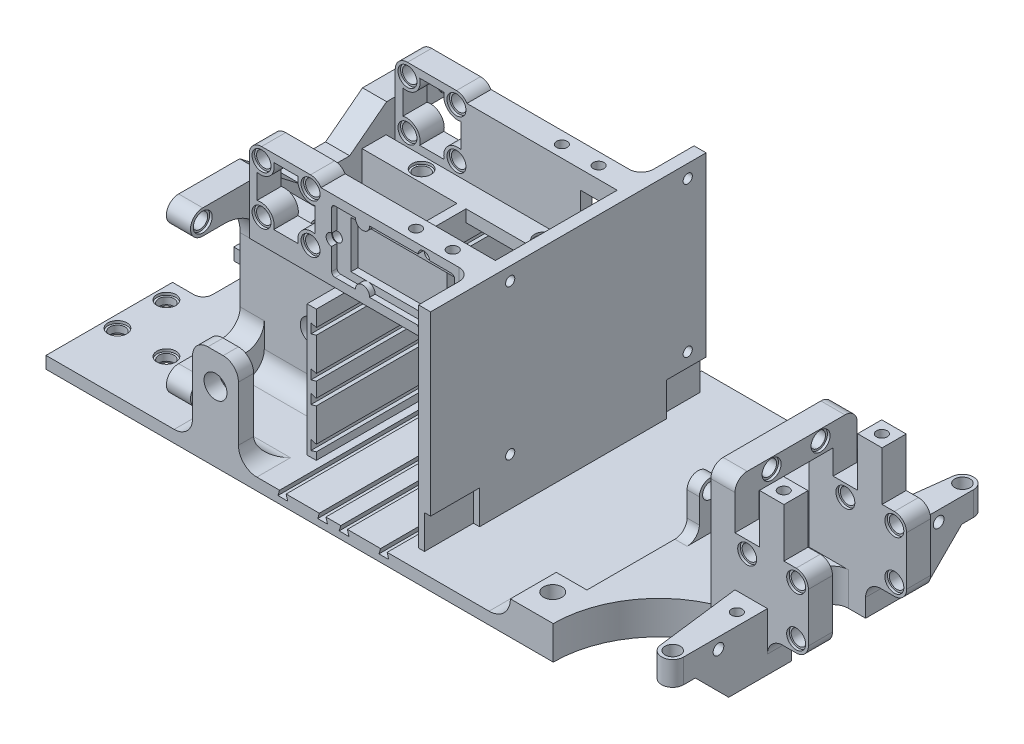
SolidWorks part; units mm, degrees
note: The reader was unsure of these and kept them because the rebuilt part matched: shared geometry of "Croquis3<3>", "Croquis3<4>", "Croquis4<3>", "Croquis6<5>", "Croquis10<3>", "Croquis12<5>", "Croquis12<4>", "Croquis13<5>", "Croquis14<3>", "Croquis25<3>", "Croquis30<3>", "Croquis24<4>", "Croquis30<5>".
material "PET"
ref_plane "Alzado" through (0, 0, 0) normal (0, 0, 1) x (1, 0, 0)
ref_plane "Planta" through (0, 0, 0) normal (0, 1, 0) x (1, 0, 0)
ref_plane "Vista lateral" through (0, 0, 0) normal (1, 0, 0) x (0, 0, -1)
sketch "Croquis1" plane through (0, 0, 0) normal (0, 0, 1) x (1, 0, 0)
  circle A0 centre (0, 15) radius 14.5 construction
  circle A1 centre (0, 15) radius 15 construction
  dimension "D2" = 30
  dimension "D3" = 29
  dimension "D1" = 15
sketch "Croquis2" plane through (0, 0, 0) normal (0, 1, 0) x (1, 0, 0)
  line L0 (-14.5, 0) -> (14.5, 0) construction
  line L1 (-15.5, 12.05) -> (15.5, 12.05)
  line L2 (-15.5, 12.05) -> (-15.5, -12.05)
  line L3 (-15.5, -12.05) -> (15.5, -12.05)
  line L4 (15.5, 12.05) -> (15.5, -12.05)
  line L5 (-15.5, 12.05) -> (15.5, -12.05) construction
  line L6 (-15.5, -12.05) -> (15.5, 12.05) construction
  line L7 (-23.37, 19.9) -> (18.5, 19.9)
  line L9 (-23.37, -19.9) -> (18.5, -19.9)
  line L11 (23.35, 19.9) -> (23.35, -19.9) construction
  line L12 (-23.35, 19.9) -> (-23.35, -19.9) construction
  line L13 (-23.37, 19.9) -> (-23.37, -19.9)
  line L14 (18.5, -19.9) -> (18.5, 19.9)
  line L16 (-23.35, 19.9) -> (23.35, 19.9) construction
  line L17 (-23.35, -19.9) -> (23.35, -19.9) construction
  point P0 (0, 0)
  dimension "D1" = 31
  dimension "D2" = 24.1
  dimension "D4" = 39.8
  dimension "D5" = 3
  dimension "D6" = 7.87
  dimension "D3" = 7.85
extrude "Saliente-Extruir1" add sketch "Croquis2" along normal blind 42.87 and the other way blind 3.9
sketch "Croquis5" plane through (0, 0, 19.9) normal (0, 0, 1) x (1, 0, 0)
  circle A0 centre (0, 15) radius 3.75
  dimension "D1" = 7.5
extrude "Cortar-Extruir4" cut sketch "Croquis5" against normal through all
sketch "Croquis3" plane through (0, 42.87, 0) normal (0, 1, 0) x (1, 0, 0)
  line L1 (-15.5, 0) -> (15.5, 0) construction
  line L2 (-15.5, 12.05) -> (-15.5, -12.05) construction
  line L3 (15.5, -12.05) -> (15.5, 12.05) construction
  circle A0 centre (0, -16) radius 2.485
  circle A1 centre (0, -16) radius 3.1
  dimension "D2" = 6.2
  dimension "D1" = 16
  dimension "D3" = 4.97
extrude "Cortar-Extruir1" cut sketch "Croquis3" against normal blind 7.87 contours A0
extrude "Cortar-Extruir2" cut sketch "Croquis3<3>" against normal blind 0.85 contours A0 | A1
sketch "Croquis3<3>" plane through (0, 42.87, 0) normal (0, 1, 0) x (1, 0, 0) same geometry as "Croquis3"
extrude "Cortar-Extruir3" cut sketch "Croquis3<4>" along normal blind 0.85 from offset 7.87 offset against normal yes
sketch "Croquis3<4>" plane through (0, 42.87, 0) normal (0, 1, 0) x (1, 0, 0) same geometry as "Croquis3"
mirror "Simetría1" about plane through (0, 0, 0) normal (0, 0, 1) of "Cortar-Extruir3", "Cortar-Extruir2", "Cortar-Extruir1"
sketch "Croquis4" plane through (0, 42.87, 0) normal (0, 1, 0) x (1, 0, 0)
  line L0 (-23.37, -19.9) -> (18.5, -19.9) construction
  line L6 (18.4996, -19.9) -> (60, -19.9)
  line L7 (18.4996, -19.9) -> (18.4996, -12)
  line L8 (18.4996, -12) -> (60, -12)
  line L9 (60, -19.9) -> (60, -12)
  circle A0 centre (40, -16) radius 2.485
  circle A1 centre (0, -16) radius 3.1 construction
  circle A2 centre (40, -16) radius 3.1
  circle A3 centre (56, -16) radius 2.485
  circle A4 centre (56, -16) radius 3.1
  point P14 (0, 0)
  dimension "D4" = 4.97
  dimension "D7" = 4
  dimension "D5" = 6.2
  dimension "D1" = 7.9
  dimension "D2" = 40
  dimension "D3" = 16
  dimension "D6" = 16
extrude "Saliente-Extruir2" add sketch "Croquis4" against normal blind 3.935
extrude "Saliente-Extruir3" add sketch "Croquis4<3>" against normal offset from surface (2.235 mm away) 0.85 from offset 0.85 contours A2 | A0 | A4 | A3 up to face at (56, 38.935, 19.1) offset against normal yes
sketch "Croquis4<3>" plane through (0, 42.87, 0) normal (0, 1, 0) x (1, 0, 0) same geometry as "Croquis4"
mirror "Simetría11" about plane through (0, 0, 0) normal (0, 0, 1) of "Saliente-Extruir2"
mirror "Simetría13" about plane through (0, 0, 0) normal (0, 0, 1) of "Saliente-Extruir3"
ref_plane "Plano2" through (0, -7.8, 0) normal (0, 1, 0) x (1, 0, 0)
sketch "Croquis6" plane through (0, -7.8, 0) normal (0, 1, 0) x (1, 0, 0)
  line L1 (-55.37, -51.335) -> (138.33, -51.335)
  line L2 (-55.37, -51.335) -> (-55.37, 51.335)
  line L5 (-23.37, 19.9) -> (-23.37, -19.9) construction
  line L6 (0, 0) -> (-55.37, 0) construction
  line L7 (-55.37, 51.335) -> (138.33, 51.335)
  line L8 (-15.5, 12.05) -> (15.5, 12.05)
  line L9 (-15.5, 12.05) -> (-15.5, -12.05)
  line L10 (-15.5, -12.05) -> (15.5, -12.05)
  line L11 (15.5, 12.05) -> (15.5, -12.05)
  line L12 (138.33, 51.335) -> (138.33, -51.335)
  circle A0 centre (-51.37, -16) radius 3.1
  circle A2 centre (-51.37, -32) radius 3.1
  circle A3 centre (-35.37, -32) radius 3.1
  circle A4 centre (-35.37, -32) radius 2.485
  circle A5 centre (-51.37, -32) radius 2.485
  circle A7 centre (-51.37, -16) radius 2.485
  circle A8 centre (-51.37, 16) radius 2.485
  circle A10 centre (-51.37, 32) radius 2.485
  circle A11 centre (-35.37, 32) radius 2.485
  circle A12 centre (-35.37, 32) radius 3.1
  circle A13 centre (-51.37, 32) radius 3.1
  circle A15 centre (-51.37, 16) radius 3.1
  dimension "D5" = 4.97
  dimension "D6" = 6.2
  dimension "D1" = 102.67
  dimension "D2" = 51.335
  dimension "D4" = 193.7
  dimension "D10" = 16
  dimension "D8" = 16
  dimension "D7" = 16
  dimension "D9" = 4
  dimension "D3" = 32
extrude "Saliente-Extruir4" add sketch "Croquis6" along normal blind 3.935
extrude "Saliente-Extruir6" add sketch "Croquis6<5>" along normal offset from surface (2.235 mm away) 0.85 from offset 0.85 contours A2 A5 | A0 A7 | A3 A4 | A12 A11 | A13 A10 | A15 A8
sketch "Croquis6<5>" plane through (0, -7.8, 0) normal (0, 1, 0) x (1, 0, 0) same geometry as "Croquis6"
sketch "Croquis9" plane through (0, -7.8, 0) normal (0, -1, 0) x (1, 0, 0)
  line L0 (-55.37, 51.335) -> (-55.37, -51.335) construction
  line L1 (-55.37, 10) -> (-48.37, 10)
  line L2 (-55.37, 10) -> (-55.37, -10)
  line L3 (-55.37, -10) -> (-48.37, -10)
  line L4 (-45.37, 7) -> (-45.37, -7)
  arc A0 (-48.37, -10) -> (-45.37, -7) centre (-48.37, -7) ccw
  arc A1 (-48.37, 10) -> (-45.37, 7) centre (-48.37, 7) cw
  point P6 (-55.37, 0)
  point P12 (-45.37, 10)
  dimension "D3" = 3
  dimension "D1" = 20
  dimension "D2" = 10
extrude "Cortar-Extruir7" cut sketch "Croquis9" against normal up to next
sketch "Croquis10" plane through (-23.37, 0, 0) normal (-1, 0, 0) x (0, 0, 1)
  line L0 (-19.9, -3.865) -> (-19.9, 42.87) construction
  line L1 (-19.9, 4.135) -> (-40, 4.135)
  line L3 (-10, -3.865) -> (-51.335, -3.865) construction
  line L4 (-40, -3.865) -> (-19.9, -3.865)
  line L5 (-19.9, -3.865) -> (-19.9, 4.135)
  line L6 (-8, 42.87) -> (-20.0744, 52.135)
  line L8 (-20.0744, 52.135) -> (-40, 52.135)
  line L9 (-40, 44.135) -> (-32.9, 44.135)
  line L10 (-19.9, 31.135) -> (-19.9, 42.87)
  line L11 (-19.9, 42.87) -> (-8, 42.87)
  line L12 (0, 0) -> (0, 42.87) construction
  line L13 (-19.9, 42.87) -> (19.9, 42.87) construction
  circle A0 centre (-40, 48.135) radius 2.485
  circle A1 centre (-40, 0.135) radius 2.485
  circle A4 centre (-40, 48.135) radius 3.1
  circle A5 centre (-40, 0.135) radius 3.1
  arc A9 (-40, 52.135) -> (-40, 44.135) centre (-40, 48.135) ccw
  arc A10 (-32.9, 44.135) -> (-19.9, 31.135) centre (-32.9, 31.135) cw
  arc A11 (-40, 4.135) -> (-40, -3.865) centre (-40, 0.135) ccw
  point P10 (0, 0)
  point P11 (0, 42.87)
  point P18 (0, 42.87)
  dimension "D1" = 4.97
  dimension "D2" = 6.2
  dimension "D8" = 4
  dimension "D10" = 13
  dimension "D7" = 8
  dimension "D9" = 35
  dimension "D11" = 8
  dimension "D3" = 40
  dimension "D4" = 48
  dimension "D5" = 4
  dimension "D6" = 37.5
  dimension "D12" = 40
extrude "Saliente-Extruir7" add sketch "Croquis10" against normal blind 7.87
extrude "Saliente-Extruir8" add sketch "Croquis10<3>" against normal offset from surface (6.17 mm away) 0.85 from offset 0.85 contours A5 A1 | A4 A0 up to face at (-15.5, 0.135, -36.9) offset against normal yes
sketch "Croquis10<3>" plane through (-23.37, 0, 0) normal (-1, 0, 0) x (0, 0, 1) same geometry as "Croquis10"
mirror "Simetría14" about plane through (0, 0, 0) normal (0, 0, 1) of "Saliente-Extruir8", "Saliente-Extruir7"
sketch "Croquis12" plane through (0, 0, 19.9) normal (0, 0, 1) x (1, 0, 0)
  line L0 (-23.37, 44.135) -> (-23.37, 31.135) construction
  line L1 (-15.5, 42.87) -> (60, 42.87) construction
  line L2 (-0.52, 38.935) -> (-0.52, 66.87) construction
  line L3 (-8.52, 66.87) -> (7.48, 66.87)
  line L4 (-12.52, 62.87) -> (-12.52, 38.935)
  line L5 (-12.52, 38.935) -> (11.48, 38.935)
  line L6 (11.48, 62.87) -> (11.48, 38.935)
  line L7 (11.48, 54.87) -> (-12.52, 54.87) construction
  line L8 (3.48, 45.37) -> (-4.52, 45.37)
  line L9 (-10.02, 50.87) -> (-10.02, 58.87)
  line L10 (8.98, 50.87) -> (8.98, 58.87)
  line L11 (3.48, 64.37) -> (-4.52, 64.37)
  line L12 (18.5, 38.935) -> (60, 38.935) construction
  circle A0 centre (-8.52, 62.87) radius 2.485
  circle A1 centre (-8.52, 62.87) radius 3.1
  circle A2 centre (7.48, 62.87) radius 2.485
  circle A3 centre (7.48, 62.87) radius 3.1
  circle A4 centre (7.48, 46.87) radius 2.485
  circle A5 centre (7.48, 46.87) radius 3.1
  circle A6 centre (-8.52, 46.87) radius 2.485
  circle A7 centre (-8.52, 46.87) radius 3.1
  arc A8 (7.48, 66.87) -> (11.48, 62.87) centre (7.48, 62.87) cw
  arc A9 (-8.52, 66.87) -> (-12.52, 62.87) centre (-8.52, 62.87) ccw
  arc A10 (-4.52, 45.37) -> (-10.02, 50.87) centre (-8.8708, 46.5192) ccw
  arc A11 (3.48, 45.37) -> (8.98, 50.87) centre (7.8308, 46.5192) cw
  arc A12 (3.48, 64.37) -> (8.98, 58.87) centre (7.8308, 63.2208) ccw
  arc A13 (-4.52, 64.37) -> (-10.02, 58.87) centre (-8.8708, 63.2208) cw
  point P34 (-0.52, 45.37)
  point P38 (8.98, 54.87)
  point P43 (-10.02, 54.87)
  line M31 (60, 42.87) -> (-15.5, 42.87)
  dimension "D8" = 4
  dimension "D3" = 6.2
  dimension "D4" = 4.97
  dimension "D10" = 4
  dimension "D17" = 4.5
  dimension "D1" = 16
  dimension "D2" = 16
  dimension "D5" = 14.85
  dimension "D6" = 4
  dimension "D7" = 4
  dimension "D9" = 4
  dimension "D12" = 12
  dimension "D13" = 2.5
  dimension "D14" = 4
  dimension "D15" = 4
  dimension "D16" = 2.5
extrude "Saliente-Extruir11" add sketch "Croquis12" along normal blind 7.87 contours L3 A9 L4 L6 A8 A13 L11 A12 L10 A11 L8 A10 L9 A1 A3 A5 A7 M31 | L6 L4 L5 M31
extrude "Saliente-Extruir15" add sketch "Croquis12<5>" along normal offset from surface (6.17 mm away) 0.85 from offset 0.85 contours A3 A2 | A5 A4 | A1 A0 | A7 A6 up to face at (-0.52, 54.87, 27.77)
sketch "Croquis12<5>" plane through (0, 0, 19.9) normal (0, 0, 1) x (1, 0, 0) same geometry as "Croquis12"
mirror "Simetría31" about plane through (0, 0, 0) normal (0, 0, 1) of "Saliente-Extruir11"
extrude "Saliente-Extruir13" add sketch "Croquis12<4>" against normal offset from surface (6.17 mm away) 0.85 from offset 40.65 contours A3 A2 | A1 A0 | A7 A6 | A5 A4 offset against normal yes
sketch "Croquis12<4>" plane through (0, 0, 19.9) normal (0, 0, 1) x (1, 0, 0) same geometry as "Croquis12"
sketch "Croquis13" plane through (0, 0, 19.9) normal (0, 0, 1) x (1, 0, 0)
  line L0 (11.48, 62.87) -> (11.48, 38.935) construction
  line L1 (15.48, 61.935) -> (22.08, 61.935)
  line L2 (14.48, 60.935) -> (14.48, 53.735)
  line L3 (15.48, 41.935) -> (22.08, 41.935)
  line L4 (54.48, 60.935) -> (54.48, 54.335)
  line L5 (14.48, 61.935) -> (54.48, 41.935) construction
  line L6 (14.48, 41.935) -> (54.48, 61.935) construction
  line L7 (14.48, 51.935) -> (12.58, 51.935)
  line L8 (26.88, 61.935) -> (42.68, 61.935)
  line L9 (60, 38.935) -> (11.48, 38.935)
  line L10 (60, 38.935) -> (60, 64.935)
  line L11 (60, 64.935) -> (11.48, 64.935)
  line L12 (11.48, 38.935) -> (11.48, 64.935)
  line L13 (26.88, 41.935) -> (42.68, 41.935)
  line L14 (54.48, 49.535) -> (54.48, 42.935)
  line L15 (46.28, 41.935) -> (53.48, 41.935)
  line L16 (46.28, 61.935) -> (53.48, 61.935)
  line L17 (14.48, 50.135) -> (14.48, 42.935)
  line L18 (14.38, 50.0376) -> (14.38, 42.935)
  line L19 (15.48, 41.835) -> (22.1822, 41.835)
  line L20 (26.7778, 41.835) -> (42.5826, 41.835)
  line L21 (46.3774, 41.835) -> (53.48, 41.835)
  line L22 (54.58, 49.6372) -> (54.58, 42.935)
  line L23 (54.58, 60.935) -> (54.58, 54.2328)
  line L24 (46.3774, 62.035) -> (53.48, 62.035)
  line L25 (26.7778, 62.035) -> (42.5826, 62.035)
  line L26 (15.48, 62.035) -> (22.1822, 62.035)
  line L27 (14.38, 60.935) -> (14.38, 53.8324)
  line L28 (11.48, 64.935) -> (10.9058, 64.935)
  arc A0 (53.48, 41.935) -> (54.48, 42.935) centre (53.48, 42.935) ccw
  arc A1 (53.48, 61.935) -> (54.48, 60.935) centre (53.48, 60.935) cw
  arc A2 (14.48, 42.935) -> (15.48, 41.935) centre (15.48, 42.935) ccw
  arc A3 (15.48, 61.935) -> (14.48, 60.935) centre (15.48, 60.935) ccw
  arc A4 (54.48, 54.335) -> (54.48, 49.535) centre (54.48, 51.935) ccw
  arc A5 (22.08, 61.935) -> (26.88, 61.935) centre (24.48, 61.935) ccw
  arc A6 (26.88, 41.935) -> (22.08, 41.935) centre (24.48, 41.935) ccw
  circle A7 centre (14.48, 51.935) radius 1.1
  arc A8 (14.48, 53.735) -> (14.48, 50.135) centre (14.48, 51.935) ccw
  circle A9 centre (44.48, 61.935) radius 1.1
  arc A10 (46.28, 61.935) -> (42.68, 61.935) centre (44.48, 61.935) ccw
  circle A11 centre (44.48, 41.935) radius 1.1
  arc A12 (42.68, 41.935) -> (46.28, 41.935) centre (44.48, 41.935) ccw
  arc A13 (14.38, 53.8324) -> (14.38, 50.0376) centre (14.48, 51.935) ccw
  arc A14 (14.38, 42.935) -> (15.48, 41.835) centre (15.48, 42.935) ccw
  arc A15 (26.7778, 41.835) -> (22.1822, 41.835) centre (24.48, 41.935) ccw
  arc A16 (42.5826, 41.835) -> (46.3774, 41.835) centre (44.48, 41.935) ccw
  arc A17 (53.48, 41.835) -> (54.58, 42.935) centre (53.48, 42.935) ccw
  arc A18 (54.58, 54.2328) -> (54.58, 49.6372) centre (54.48, 51.935) ccw
  arc A19 (53.48, 62.035) -> (54.58, 60.935) centre (53.48, 60.935) cw
  arc A20 (46.3774, 62.035) -> (42.5826, 62.035) centre (44.48, 61.935) ccw
  arc A21 (22.1822, 62.035) -> (26.7778, 62.035) centre (24.48, 61.935) ccw
  arc A22 (15.48, 62.035) -> (14.38, 60.935) centre (15.48, 60.935) ccw
  arc A23 (11.48, 62.87) -> (7.48, 66.87) centre (7.48, 62.87) ccw construction
  arc A24 (11.48, 62.87) -> (7.48, 66.87) centre (7.48, 62.87) ccw
  point P0 (34.48, 51.935)
  point P46 (10.9058, 64.935)
  dimension "D3" = 1
  dimension "D5" = 4.8
  dimension "D6" = 3.6
  dimension "D7" = 2.2
  dimension "D1" = 40
  dimension "D2" = 20
  dimension "D4" = 30
  dimension "D8" = 10
  dimension "D9" = 3
  dimension "D10" = 3
  dimension "D12" = 3
  dimension "D13" = 10
  dimension "D14" = 0.1
extrude "Saliente-Extruir14" add sketch "Croquis13" along normal blind 7.87 contours A24 L12 L28
extrude "Cortar-Extruir8" cut sketch "Croquis13<5>" against normal blind 1.8 from surface at 7.87 contours L26 A21 L25 A20 L24 A19 L23 A18 L22 A17 L21 A16 L20 A15 L19 A14 L18 A13 L27 A22 starting at face at (14.8931, 57.947, 27.77)
sketch "Croquis13<5>" plane through (0, 0, 19.9) normal (0, 0, 1) x (1, 0, 0) same geometry as "Croquis13"
sketch "Croquis14" plane through (0, 0, 25.97) normal (0, 0, 1) x (1, 0, 0)
  line L0 (60, 62.035) -> (60, 41.835) construction
  line L2 (60, 59.635) -> (18.88, 59.635)
  line L3 (18.88, 59.635) -> (18.88, 44.235)
  line L4 (18.88, 44.235) -> (60, 44.235)
  line L11 (53.48, 62.035) -> (46.3774, 62.035)
  line L21 (42.5826, 62.035) -> (26.7778, 62.035)
  line L22 (22.1822, 62.035) -> (15.48, 62.035)
  line L23 (14.38, 60.935) -> (14.38, 53.8324)
  line L24 (14.38, 50.0376) -> (14.38, 42.935)
  line L25 (15.48, 41.835) -> (22.1822, 41.835)
  line L26 (26.7778, 41.835) -> (42.5826, 41.835)
  line L27 (46.3774, 41.835) -> (53.48, 41.835)
  line L28 (54.58, 42.935) -> (54.58, 49.6372)
  line L29 (53.48, 62.035) -> (46.3774, 62.035)
  line L30 (42.5826, 62.035) -> (26.7778, 62.035)
  line L31 (22.1822, 62.035) -> (15.48, 62.035)
  line L32 (14.38, 60.935) -> (14.38, 53.8324)
  line L33 (14.38, 50.0376) -> (14.38, 42.935)
  line L34 (15.48, 41.835) -> (22.1822, 41.835)
  line L35 (26.7778, 41.835) -> (42.5826, 41.835)
  line L36 (46.3774, 41.835) -> (53.48, 41.835)
  line L43 (54.58, 42.935) -> (54.58, 49.6372)
  line L44 (54.58, 54.2328) -> (54.58, 60.935)
  line L45 (54.58, 54.2328) -> (54.58, 60.935)
  circle A0 centre (14.48, 51.935) radius 1.6
  circle A1 centre (44.48, 61.935) radius 1.6
  circle A2 centre (44.48, 41.935) radius 1.6
  arc A19 (46.3774, 62.035) -> (42.5826, 62.035) centre (44.48, 61.935) ccw
  arc A20 (22.1822, 62.035) -> (26.7778, 62.035) centre (24.48, 61.935) ccw
  arc A21 (15.48, 62.035) -> (14.38, 60.935) centre (15.48, 60.935) ccw
  arc A22 (14.38, 53.8324) -> (14.38, 50.0376) centre (14.48, 51.935) ccw
  arc A23 (14.38, 42.935) -> (15.48, 41.835) centre (15.48, 42.935) ccw
  arc A24 (26.7778, 41.835) -> (22.1822, 41.835) centre (24.48, 41.935) ccw
  arc A25 (42.5826, 41.835) -> (46.3774, 41.835) centre (44.48, 41.935) ccw
  arc A26 (46.3774, 62.035) -> (42.5826, 62.035) centre (44.48, 61.935) ccw
  arc A27 (22.1822, 62.035) -> (26.7778, 62.035) centre (24.48, 61.935) ccw
  arc A28 (15.48, 62.035) -> (14.38, 60.935) centre (15.48, 60.935) ccw
  arc A33 (14.38, 53.8324) -> (14.38, 50.0376) centre (14.48, 51.935) ccw
  arc A34 (14.38, 42.935) -> (15.48, 41.835) centre (15.48, 42.935) ccw
  arc A35 (26.7778, 41.835) -> (22.1822, 41.835) centre (24.48, 41.935) ccw
  arc A36 (42.5826, 41.835) -> (46.3774, 41.835) centre (44.48, 41.935) ccw
  arc A43 (54.58, 60.935) -> (53.48, 62.035) centre (53.48, 60.935) ccw
  arc A44 (54.58, 60.935) -> (53.48, 62.035) centre (53.48, 60.935) ccw
  arc A45 (53.48, 41.835) -> (54.58, 42.935) centre (53.48, 42.935) ccw
  arc A46 (53.48, 41.835) -> (54.58, 42.935) centre (53.48, 42.935) ccw
  arc A47 (54.58, 54.2328) -> (54.58, 49.6372) centre (54.48, 51.935) ccw
  arc A48 (54.58, 54.2328) -> (54.58, 49.6372) centre (54.48, 51.935) ccw
  dimension "D2" = 3.2
  dimension "D5" = 4.5
  dimension "D1" = 0
extrude "Cortar-Extruir10" cut sketch "Croquis14" against normal blind 2.3
mirror "Simetría34" about plane through (0, 0, 0) normal (0, 0, 1) of "Cortar-Extruir10", "Saliente-Extruir14"
extrude "Cortar-Extruir11" cut sketch "Croquis14<3>" along normal blind 1.8 from surface at -53.74
sketch "Croquis14<3>" plane through (0, 0, 25.97) normal (0, 0, 1) x (1, 0, 0) same geometry as "Croquis14"
sketch "Croquis18" plane through (0, 0, -27.77) normal (0, 0, -1) x (-1, 0, 0)
  line L0 (-60, 44.235) -> (-60, 59.635) construction
  line L1 (-60, 58.935) -> (-48, 58.935)
  line L2 (-60, 58.935) -> (-60, 44.935)
  line L3 (-60, 44.935) -> (-48, 44.935)
  line L4 (-48, 58.935) -> (-48, 44.935)
  point P6 (-60, 51.935)
  point P8 (-60, 51.935)
  dimension "D1" = 14
  dimension "D2" = 12
extrude "Cortar-Extruir14" cut sketch "Croquis18" against normal through all contours L2 L3 L4 L1
sketch "Croquis23" plane through (0, -3.865, 0) normal (0, 1, 0) x (1, 0, 0)
  line L0 (-55.37, -51.335) -> (138.33, -51.335) construction
  line L1 (138.33, 51.335) -> (106.33, 51.335)
  line L2 (138.33, 51.335) -> (138.33, -51.335)
  line L3 (138.33, -51.335) -> (106.33, -51.335)
  line L4 (106.33, 51.335) -> (106.33, -51.335)
  dimension "D1" = 32
extrude "Saliente-Extruir16" add sketch "Croquis23" along normal blind 6.97
sketch "Croquis25" plane through (138.33, 0, 0) normal (1, 0, 0) x (0, 0, -1)
  line L0 (-12.1, 3.105) -> (-12.1, 35.105)
  line L1 (-51.335, 3.105) -> (51.335, 3.105) construction
  line L2 (-12.1, 35.105) -> (12.1, 35.105)
  line L3 (12.1, 35.105) -> (12.1, 3.105)
  line L4 (12.1, 3.105) -> (19.97, 3.105)
  line L5 (19.97, 3.105) -> (19.97, 38.505)
  line L6 (15.97, 42.505) -> (-15.97, 42.505)
  line L7 (-19.97, 38.505) -> (-19.97, 3.105)
  line L8 (-19.97, 3.105) -> (-12.1, 3.105)
  arc A0 (19.97, 38.505) -> (15.97, 42.505) centre (15.97, 38.505) ccw
  arc A1 (-15.97, 42.505) -> (-19.97, 38.505) centre (-15.97, 38.505) ccw
  circle A4 centre (-8, 39.105) radius 3.1
  circle A5 centre (8, 39.105) radius 3.1
  circle A6 centre (8, 39.105) radius 2.485
  circle A7 centre (-8, 39.105) radius 2.485
  point P25 (-8.931, 38.599)
  point P26 (0, 0)
  point P27 (0, 0)
  point P28 (-7.3916, 36.4142)
  line M13 (51.335, 3.105) -> (-51.335, 3.105)
  dimension "D10" = 16
  dimension "D3" = 32
  dimension "D8" = 4
  dimension "D6" = 4.97
  dimension "D7" = 6.2
  dimension "D11" = 4
  dimension "D1" = 12.1
  dimension "D2" = 24.2
  dimension "D4" = 7.4
  dimension "D5" = 7.87
  dimension "D9" = 8
extrude "Saliente-Extruir18" add sketch "Croquis25" against normal blind 7.87 contours L6 A1 L7 L0 L2 L3 L5 A0 A5 A4 M13
extrude "Saliente-Extruir19" add sketch "Croquis25<3>" against normal offset from surface (6.17 mm away) 0.85 from offset 0.85 contours A4 A7 | A5 A6 up to face at (130.46, 39.105, -11.1) offset against normal yes
sketch "Croquis25<3>" plane through (138.33, 0, 0) normal (1, 0, 0) x (0, 0, -1) same geometry as "Croquis25"
sketch "Croquis27" plane through (106.33, 0, 0) normal (-1, 0, 0) x (0, 0, 1)
  line L0 (3.6, 3.105) -> (-3.6, 3.105)
  line L1 (12.1, 3.105) -> (-12.1, 3.105) construction
  line L2 (-3.6, 3.105) -> (-3.6, 15.105)
  line L3 (3.6, 15.105) -> (3.6, 3.105)
  line L4 (0, 0) -> (0, 30) construction
  arc A0 (-3.6, 15.105) -> (3.6, 15.105) centre (0, 15.105) cw
  circle A1 centre (0, 15.105) radius 2.525
  point P7 (0, 3.105)
  dimension "D2" = 5.05
  dimension "D1" = 7.2
  dimension "D3" = 12
extrude "Saliente-Extruir20" add sketch "Croquis27" against normal blind 4
sketch "Croquis30" plane through (0, 0, 12.1) normal (0, 0, -1) x (-1, 0, 0)
  line L0 (-138.33, 3.105) -> (-158.33, 3.105)
  line L1 (-162.33, 7.105) -> (-162.33, 23.105)
  line L2 (-158.33, 27.105) -> (-138.33, 27.105)
  line L3 (-138.33, 38.505) -> (-138.33, 3.105) construction
  line L4 (-138.33, 27.105) -> (-138.33, 3.105)
  arc A0 (-158.33, 3.105) -> (-162.33, 7.105) centre (-158.33, 7.105) cw
  arc A1 (-162.33, 23.105) -> (-158.33, 27.105) centre (-158.33, 23.105) cw
  circle A2 centre (-142.33, 23.105) radius 2.485
  circle A3 centre (-142.33, 23.105) radius 3.1
  circle A4 centre (-158.33, 23.105) radius 2.485
  circle A5 centre (-158.33, 23.105) radius 3.1
  circle A6 centre (-158.33, 7.105) radius 2.485
  circle A7 centre (-158.33, 7.105) radius 3.1
  point P20 (0, 0)
  point P21 (0, 0)
  point P22 (-189.936, 23.105)
  point P23 (-169.35, 23.105)
  point P24 (-185.35, 7.105)
  point P25 (-185.35, 23.105)
  line M12 (-138.33, 35.105) -> (-138.33, 3.105)
  dimension "D1" = 4.97
  dimension "D2" = 6.2
  dimension "D8" = 4
  dimension "D5" = 4
  dimension "D9" = 4
  dimension "D3" = 16
  dimension "D4" = 16
  dimension "D7" = 20
  dimension "D6" = 4
extrude "Saliente-Extruir21" add sketch "Croquis30" against normal blind 7.87 contours A1 L1 A0 L0 L2 A7 A5 A3 M12
extrude "Saliente-Extruir22" add sketch "Croquis30<3>" against normal offset from surface (6.17 mm away) 0.85 from offset 0.85 contours A3 A2 | A5 A4 | A7 A6 up to face at (146.543, 18.9717, 19.97) offset against normal yes
sketch "Croquis30<3>" plane through (0, 0, 12.1) normal (0, 0, -1) x (-1, 0, 0) same geometry as "Croquis30"
sketch "Croquis24" plane through (0, 3.105, 0) normal (0, 1, 0) x (1, 0, 0)
  line L0 (138.33, -51.335) -> (138.33, -19.97) construction
  line L1 (106.33, -51.335) -> (138.33, -51.335) construction
  line L2 (145.35, -47.33) -> (145.35, -50.93) construction
  line L3 (148.95, -47.33) -> (148.95, -19.97)
  line L5 (158.33, -19.97) -> (138.33, -19.97) construction
  line L6 (138.33, -19.97) -> (148.95, -19.97)
  line L7 (130.46, -19.97) -> (138.33, -19.97)
  line L10 (138.33, -51.335) -> (110.33, -51.335)
  line L11 (138.33, -19.97) -> (141.7774, -47.773)
  line L16 (138.33, -51.335) -> (138.33, -19.97)
  line L17 (106.33, 51.335) -> (106.33, -51.335) construction
  circle A0 centre (145.35, -47.33) radius 2.5
  circle A5 centre (145.35, -47.33) radius 3.6
  arc A7 (110.33, -51.335) -> (130.46, -19.97) centre (144.8303, -51.335) cw
  dimension "D1" = 5
  dimension "D2" = 47.33
  dimension "D7" = 7.2
  dimension "D3" = 4
  dimension "D4" = 145.35
extrude "Cortar-Extruir15" cut sketch "Croquis24" against normal through all contours L16 L10 A7 L7
extrude "Saliente-Extruir23" add sketch "Croquis24<4>" along normal blind 7.87
sketch "Croquis24<4>" plane through (0, 3.105, 0) normal (0, 1, 0) x (1, 0, 0) same geometry as "Croquis24"
sketch "Croquis48" plane through (148.95, 0, 0) normal (1, 0, 0) x (0, 0, -1)
  line L0 (-43.53, 3.105) -> (-32.625, -7.8)
  line L1 (-47.33, 3.105) -> (-19.97, 3.105) construction
  line L2 (-51.335, -7.8) -> (-19.97, -7.8) construction
  line L3 (-32.625, -7.8) -> (-12.1, -7.8)
  line L4 (51.335, -7.8) -> (-19.97, -7.8) construction
  line L5 (-12.1, -7.8) -> (-12.1, 3.105)
  line L6 (-12.1, 3.105) -> (-43.53, 3.105)
  line L7 (-50.93, 10.975) -> (-50.93, 3.105) construction
  dimension "D1" = 7.4
  dimension "D2" = 135
extrude "Saliente-Extruir28" add sketch "Croquis48" against normal up to surface (10.62 mm away)
sketch "Croquis49" plane through (0, 3.105, 0) normal (0, 1, 0) x (1, 0, 0)
  line L3 (141.2513, -43.53) -> (138.33, -19.97)
  line L4 (138.33, -19.97) -> (138.33, -43.53)
  line L5 (138.33, -43.53) -> (141.2513, -43.53)
  line L6 (141.2513, -43.53) -> (138.33, -19.97)
  line L7 (138.33, -19.97) -> (138.33, -43.53)
  line L8 (138.33, -43.53) -> (141.2513, -43.53)
  dimension "D1" = 0
extrude "Cortar-Extruir25" cut sketch "Croquis49" against normal up to next
mirror "Simetría36" about plane through (0, 0, 0) normal (0, 0, 1) of "Cortar-Extruir25", "Saliente-Extruir28", "Saliente-Extruir21", "Cortar-Extruir15", "Saliente-Extruir23"
extrude "Saliente-Extruir24" add sketch "Croquis30<5>" along normal offset from surface (6.17 mm away) 0.85 from offset 25.05 contours A3 A2 | A5 A4 | A7 A6 up to face at (145.0444, 13.6227, -19.97)
sketch "Croquis30<5>" plane through (0, 0, 12.1) normal (0, 0, -1) x (-1, 0, 0) same geometry as "Croquis30"
fillet "Redondeo10" radius 5 3 edges at (138.33, -2.3475, -12.1) (148.95, 3.105, -16.035) (148.95, 3.105, 16.035)
sketch "Croquis52" plane through (0, -3.865, 0) normal (0, 1, 0) x (1, 0, 0)
  line L1 (106.33, 51.335) -> (96.33, 51.335)
  line L2 (106.33, 51.335) -> (106.33, 36.335)
  line L3 (106.33, 36.335) -> (96.33, 36.335)
  line L4 (96.33, 51.335) -> (96.33, 36.335)
  line L5 (106.33, -51.335) -> (96.33, -51.335)
  line L6 (106.33, -51.335) -> (106.33, -36.335)
  line L7 (106.33, -36.335) -> (96.33, -36.335)
  line L8 (96.33, -51.335) -> (96.33, -36.335)
  dimension "D1" = 10
  dimension "D2" = 15
  dimension "D3" = 15
  dimension "D4" = 10
extrude "Saliente-Extruir29" add sketch "Croquis52" along normal up to surface (6.97 mm away) up to face at (119.8824, 3.105, -0.5424)
sketch "Croquis34" plane through (0, 3.105, 0) normal (0, 1, 0) x (1, 0, 0)
  line L0 (106.33, 36.335) -> (106.33, 3.6) construction
  line L2 (106.33, 0) -> (138.33, 0) construction
  line L3 (106.33, 3.6) -> (106.33, -3.6) construction
  line L4 (138.33, 15.97) -> (138.33, -15.97) construction
  circle A6 centre (101.33, 42.5) radius 3
  circle A7 centre (101.33, -42.5) radius 3
  point P0 (101.0243, 42.5)
  dimension "D8" = 6
  dimension "D2" = 5
  dimension "D10" = 42.5
extrude "Cortar-Extruir19" cut sketch "Croquis34" against normal blind 5 contours A7 | A6
sketch "Croquis39" plane through (0, 64.935, 0) normal (0, 1, 0) x (1, 0, 0)
  line L2 (0, 0) -> (15.5, 0) construction
  line L3 (-15, 0) -> (15, 0) construction
  line L4 (15.5, -12.05) -> (15.5, 12.05) construction
  line L5 (10.9058, 27.77) -> (10.9058, 19.9) construction
  line L6 (60, 27.77) -> (60, 19.9) construction
  circle A0 centre (38, 23.835) radius 1.75
  circle A1 centre (50, 23.835) radius 1.75
  circle A2 centre (50, -23.835) radius 1.75
  circle A3 centre (38, -23.835) radius 1.75
  point P4 (15.5, 0)
  point P6 (0, 0)
  point P21 (0, 0)
  point P22 (10.9058, 23.835)
  dimension "D1" = 3.5
  dimension "D2" = 10
  dimension "D3" = 12
extrude "Cortar-Extruir20" cut sketch "Croquis39" against normal blind 5
sketch "Croquis41" plane through (0, 0, 51.335) normal (0, 0, 1) x (1, 0, 0)
  line L0 (-7.5, -3.865) -> (-7.5, 20)
  line L1 (18.5, -3.865) -> (-15.5, -3.865) construction
  line L2 (-2.5, 25) -> (2.5, 25)
  line L3 (7.5, 20) -> (7.5, -3.865)
  line L4 (-55.37, -3.865) -> (96.33, -3.865) construction
  arc A0 (-7.5, 20) -> (-2.5, 25) centre (-2.5, 20) cw
  arc A1 (2.5, 25) -> (7.5, 20) centre (2.5, 20) cw
  circle A2 centre (0, 15) radius 3.75
  line M8 (96.33, -3.865) -> (-55.37, -3.865)
  dimension "D1" = 7.5
  dimension "D5" = 5
  dimension "D2" = 7.5
  dimension "D3" = 15
  dimension "D4" = 10
extrude "Saliente-Extruir26" add sketch "Croquis41" against normal blind 4.97 contours A1 L2 A0 L0 L3 A2 M8
mirror "Simetría37" about plane through (0, 0, 0) normal (0, 0, 1) of "Saliente-Extruir26"
sketch "Croquis47" plane through (60, 0, 0) normal (1, 0, 0) x (0, 0, -1)
  line L0 (-51.335, -3.865) -> (-10, -3.865) construction
  line L1 (45, -3.865) -> (-45, -3.865)
  line L2 (45, -3.865) -> (45, 64.935)
  line L3 (45, 64.935) -> (-45, 64.935)
  line L4 (-45, -3.865) -> (-45, 64.935)
  line L5 (36.335, -3.865) -> (-36.335, -3.865) construction
  line L6 (27.77, 64.935) -> (19.9, 64.935) construction
  circle A0 centre (-19, 60.635) radius 1.5
  circle A1 centre (39, 60.635) radius 1.5
  circle A2 centre (39, 11.635) radius 1.5
  circle A3 centre (-19, 11.635) radius 1.5
  point P18 (0, 0)
  point P19 (0, 0)
  point P20 (0, 0)
  point P21 (0, 0)
  point P22 (0, 0)
  point P23 (-29, 0)
  dimension "D4" = 3
  dimension "D1" = 64.5
  dimension "D2" = 45
  dimension "D3" = 45
  dimension "D5" = 58
  dimension "D6" = 49
  dimension "D7" = 39
extrude "Saliente-Extruir27" add sketch "Croquis47" along normal blind 3.935
fillet "Redondeo7" radius 4 6 edges at (60, 41.935, 27.77) (60, 41.935, -27.77) (60, 40.9025, 12) (60, 40.9025, -12) (60, 61.935, 27.77) (60, 61.935, -27.77)
fillet "Redondeo8" radius 7.87 2 edges at (2.99, 38.935, -19.9) (2.99, 38.935, 19.9)
fillet "Redondeo9" radius 6 10 edges at (0, -3.865, -46.365) (0, -3.865, 46.365) (-7.5, -3.865, 48.85) (7.5, -3.865, 48.85) (-7.5, -3.865, -48.85) (7.5, -3.865, -48.85) (1.5, -3.865, -19.9) (1.5, -3.865, 19.9) (-19.435, 4.135, -19.9) (-19.435, 4.135, 19.9)
sketch "Croquis50" plane through (0, 10.975, 0) normal (0, 1, 0) x (1, 0, 0)
  line L3 (138.33, -19.97) -> (141.7774, -47.773)
  line L4 (148.95, -47.33) -> (148.95, -19.97)
  line L5 (148.95, -19.97) -> (138.33, -19.97)
  line L6 (138.33, -19.97) -> (141.7774, -47.773)
  line L7 (148.95, -47.33) -> (148.95, -19.97)
  line L8 (148.95, -19.97) -> (138.33, -19.97)
  circle A0 centre (144.95, -25.97) radius 1.75
  arc A1 (141.7774, -47.773) -> (148.95, -47.33) centre (145.35, -47.33) ccw
  arc A2 (141.7774, -47.773) -> (148.95, -47.33) centre (145.35, -47.33) ccw
  dimension "D2" = 3.5
  dimension "D3" = 6
  dimension "D4" = 4
  dimension "D1" = 0
extrude "Cortar-Extruir26" cut sketch "Croquis50" against normal blind 5 contours A0
sketch "Croquis51" plane through (148.95, 0, 0) normal (1, 0, 0) x (0, 0, -1)
  line L1 (-47.33, 10.975) -> (-19.97, 10.975) construction
  line L2 (-19.97, 10.975) -> (-19.97, -1.895) construction
  circle A0 centre (-35.97, 7.475) radius 1.75
  point P4 (0, 0)
  point P9 (0, 0)
  dimension "D1" = 3.5
  dimension "D2" = 16
  dimension "D4" = 3.5
extrude "Cortar-Extruir27" cut sketch "Croquis51" against normal blind 5
mirror "Simetría38" about plane through (0, 0, 0) normal (0, 0, 1) of "Cortar-Extruir27", "Cortar-Extruir26"
sketch "Croquis53" plane through (0, 27.105, 0) normal (0, 1, 0) x (1, 0, 0)
  line L0 (158.33, -12.1) -> (138.33, -12.1) construction
  line L1 (146.33, -12.1) -> (154.33, -12.1)
  line L2 (146.33, -12.1) -> (146.33, -19.97)
  line L3 (146.33, -19.97) -> (154.33, -19.97)
  line L4 (154.33, -12.1) -> (154.33, -19.97)
  line L5 (158.33, -19.97) -> (138.33, -19.97) construction
  line L6 (158.33, 19.97) -> (138.33, 19.97) construction
  line L7 (146.33, 19.97) -> (154.33, 19.97)
  line L8 (146.33, 19.97) -> (146.33, 12.1)
  line L9 (146.33, 12.1) -> (154.33, 12.1)
  line L10 (154.33, 19.97) -> (154.33, 12.1)
  line L11 (158.33, 12.1) -> (138.33, 12.1) construction
  line L14 (162.33, -19.97) -> (162.33, -12.1) construction
  point P20 (150.33, -12.1)
  dimension "D1" = 12
  dimension "D2" = 8
extrude "Saliente-Extruir30" add sketch "Croquis53" along normal blind 16
sketch "Croquis54" plane through (0, 43.105, 0) normal (0, 1, 0) x (1, 0, 0)
  line L0 (146.33, 12.1) -> (154.33, 12.1) construction
  line L1 (146.33, 19.97) -> (146.33, 12.1) construction
  line L2 (146.33, -12.1) -> (146.33, -19.97) construction
  circle A0 centre (150.33, 16.035) radius 1.75
  circle A1 centre (150.33, -16.035) radius 1.75
  point P4 (0, 0)
  point P7 (150.33, 12.1)
  point P8 (0, 0)
  point P11 (146.33, 16.035)
  point P14 (0, 0)
  point P15 (146.33, -16.035)
  dimension "D1" = 3.5
extrude "Cortar-Extruir28" cut sketch "Croquis54" against normal blind 5
fillet "Redondeo11" radius 6.97 5 edges at (96.33, -3.865, 43.835) (101.33, -3.865, 36.335) (106.33, -3.865, 0) (101.33, -3.865, -36.335) (96.33, -3.865, -43.835)
sketch "Croquis55" plane through (63.935, 0, 0) normal (1, 0, 0) x (0, 0, -1)
  line L0 (40.365, -3.865) -> (51.335, -3.865) construction
  line L1 (45, -3.865) -> (32, -3.865)
  line L2 (45, -3.865) -> (45, 7.135)
  line L3 (45, 7.135) -> (32, 7.135)
  line L4 (32, -3.865) -> (32, 7.135)
  line L5 (10, -3.865) -> (51.335, -3.865) construction
  line L6 (45, -3.865) -> (45, 64.935) construction
  line L7 (-51.335, -3.865) -> (-10, -3.865) construction
  line L8 (-45, -3.865) -> (-29, -3.865)
  line L9 (-45, -3.865) -> (-45, 7.135)
  line L10 (-45, 7.135) -> (-29, 7.135)
  line L11 (-29, -3.865) -> (-29, 7.135)
  line L12 (-45, 64.935) -> (-45, -3.865) construction
  dimension "D1" = 11
  dimension "D2" = 13
  dimension "D3" = 11
  dimension "D4" = 16
extrude "Cortar-Extruir29" cut sketch "Croquis55" against normal blind 2
fillet "Redondeo12" radius 4 2 edges at (108.33, 3.105, 3.6) (108.33, 3.105, -3.6)
sketch "Croquis56" plane through (0, -3.865, 0) normal (0, 1, 0) x (1, 0, 0)
  line L0 (60, 19.9) -> (10.9058, 19.9) construction
  line L1 (18.5, 19.9) -> (15.5, 19.9)
  line L2 (18.5, 19.9) -> (18.5, 36.9)
  line L3 (18.5, 36.9) -> (15.5, 36.9)
  line L4 (15.5, 19.9) -> (15.5, 36.9)
  line L5 (60, 19.9) -> (-12.52, 19.9) construction
  line L6 (-12.52, -19.9) -> (60, -19.9) construction
  line L7 (18.5, -19.9) -> (15.5, -19.9)
  line L8 (18.5, -19.9) -> (18.5, -36.9)
  line L9 (18.5, -36.9) -> (15.5, -36.9)
  line L10 (15.5, -19.9) -> (15.5, -36.9)
  line L11 (18.5, 25.9) -> (18.5, -25.9) construction
  line L12 (15.5, -12.05) -> (15.5, 12.05) construction
  dimension "D1" = 17
  dimension "D2" = 17
extrude "Saliente-Extruir33" add sketch "Croquis56" along normal up to surface (42.8 mm away) contours L10 L9 L8 L7 | L4 L3 L2 L1 up to face at (56, 38.935, 19.1)
sketch "Croquis57" plane through (0, 0, -51.335) normal (0, 0, -1) x (-1, 0, 0)
  line L0 (-21, -3.865) -> (-20.5, -5.565)
  line L1 (-13.5, -3.865) -> (-89.36, -3.865) construction
  line L2 (-20.5, -5.565) -> (-23.5, -5.565)
  line L3 (-23.5, -5.565) -> (-23, -3.865)
  line L4 (-23, -3.865) -> (-21, -3.865)
  line L5 (-18.5, 38.935) -> (-18.5, -3.865) construction
  line L6 (-34, -3.865) -> (-33.5, -5.565)
  line L7 (-33.5, -5.565) -> (-36.5, -5.565)
  line L8 (-36.5, -5.565) -> (-36, -3.865)
  line L9 (-36, -3.865) -> (-34, -3.865)
  line L10 (-41, -3.865) -> (-40.5, -5.565)
  line L11 (-40.5, -5.565) -> (-43.5, -5.565)
  line L12 (-43.5, -5.565) -> (-43, -3.865)
  line L13 (-43, -3.865) -> (-41, -3.865)
  line L14 (-54, -3.865) -> (-53.5, -5.565)
  line L15 (-53.5, -5.565) -> (-56.5, -5.565)
  line L16 (-56.5, -5.565) -> (-56, -3.865)
  line L17 (-56, -3.865) -> (-54, -3.865)
  line L18 (-18.5, -3.865) -> (-58.5, -3.865)
  line L19 (-56.5936, -5.635) -> (-56.0524, -3.795)
  line L20 (-56.0524, -3.795) -> (-53.9476, -3.795)
  line L21 (-53.9476, -3.795) -> (-53.4064, -5.635)
  line L22 (-53.4064, -5.635) -> (-56.5936, -5.635)
  line L23 (-40.4064, -5.635) -> (-43.5936, -5.635)
  line L24 (-43.5936, -5.635) -> (-43.0524, -3.795)
  line L25 (-43.0524, -3.795) -> (-40.9476, -3.795)
  line L26 (-40.9476, -3.795) -> (-40.4064, -5.635)
  line L27 (-33.4064, -5.635) -> (-36.5936, -5.635)
  line L28 (-36.5936, -5.635) -> (-36.0524, -3.795)
  line L29 (-36.0524, -3.795) -> (-33.9476, -3.795)
  line L30 (-33.9476, -3.795) -> (-33.4064, -5.635)
  line L31 (-20.4064, -5.635) -> (-23.5936, -5.635)
  line L32 (-23.5936, -5.635) -> (-23.0524, -3.795)
  line L33 (-23.0524, -3.795) -> (-20.9476, -3.795)
  line L34 (-20.9476, -3.795) -> (-20.4064, -5.635)
  line L35 (-18.5, -3.865) -> (-18.5, 36.135)
  line L36 (-18.5, -1.365) -> (-16.8, -1.865)
  line L37 (-16.8, -1.865) -> (-16.8, 1.135)
  line L38 (-16.8, 1.135) -> (-18.5, 0.635)
  line L39 (-18.5, 11.635) -> (-16.8, 11.135)
  line L40 (-16.8, 11.135) -> (-16.8, 14.135)
  line L41 (-16.8, 14.135) -> (-18.5, 13.635)
  line L42 (-18.5, 18.635) -> (-16.8, 18.135)
  line L43 (-16.8, 18.135) -> (-16.8, 21.135)
  line L44 (-16.8, 21.135) -> (-18.5, 20.635)
  line L45 (-18.5, 31.635) -> (-16.8, 31.135)
  line L46 (-16.8, 31.135) -> (-16.8, 34.135)
  line L47 (-16.8, 34.135) -> (-18.5, 33.635)
  line L48 (-18.5198, 31.5678) -> (-16.73, 31.0414)
  line L49 (-16.73, 31.0414) -> (-16.73, 34.2286)
  line L50 (-16.73, 34.2286) -> (-18.5198, 33.7022)
  line L51 (-18.5198, 18.5678) -> (-16.73, 18.0414)
  line L52 (-16.73, 18.0414) -> (-16.73, 21.2286)
  line L53 (-16.73, 21.2286) -> (-18.5198, 20.7022)
  line L54 (-18.5198, 11.5678) -> (-16.73, 11.0414)
  line L55 (-16.73, 11.0414) -> (-16.73, 14.2286)
  line L56 (-16.73, 14.2286) -> (-18.5198, 13.7022)
  line L57 (-18.5198, -1.4322) -> (-16.73, -1.9586)
  line L58 (-16.73, -1.9586) -> (-16.73, 1.2286)
  line L59 (-16.73, 1.2286) -> (-18.5198, 0.7022)
  point P4 (-22, -5.565)
  point P7 (-22, -3.865)
  point P12 (-35, -5.565)
  point P15 (-35, -3.865)
  point P18 (-42, -5.565)
  point P21 (-42, -3.865)
  point P24 (-55, -5.565)
  point P27 (-55, -3.865)
  point P28 (-38.5, -3.865)
  point P51 (-16.8, -0.365)
  point P56 (-16.8, 12.635)
  point P61 (-16.8, 19.635)
  point P66 (-16.8, 32.635)
  point P69 (0, 0)
  point P70 (-18.5, 16.135)
  point P71 (-18.5, 14.135)
  point P72 (-18.5, 12.9184)
  point P73 (-18.5, 11.0089)
  point P74 (-18.5, 5.6562)
  point P75 (-18.5, 3.7491)
  point P76 (-18.5, 16.135)
  point P77 (-18.5, 16.135)
  point P78 (-18.5, 16.7587)
  point P79 (-18.5, 16.135)
  point P80 (-18.5, 23.8633)
  dimension "D1" = 3
  dimension "D2" = 1.7
  dimension "D3" = 0.5
  dimension "D4" = 3.5
  dimension "D5" = 3
  dimension "D6" = 0.5
  dimension "D7" = 3
  dimension "D8" = 0.5
  dimension "D9" = 3
  dimension "D10" = 0.5
  dimension "D11" = 7
  dimension "D12" = 40
  dimension "D13" = 3.5
  dimension "D14" = 3.5
  dimension "D16" = 40
  dimension "D17" = 3.5
  dimension "D18" = 1.7
  dimension "D19" = 3
  dimension "D20" = 0.5
  dimension "D21" = 0.5
  dimension "D22" = 3
  dimension "D23" = 0.5
  dimension "D24" = 0.5
  dimension "D25" = 3
  dimension "D26" = 0.5
  dimension "D27" = 0.5
  dimension "D28" = 3
  dimension "D29" = 0.5
  dimension "D30" = 0.5
  dimension "D31" = 7
  dimension "D32" = 3.5
  dimension "D33" = 3.5
  dimension "D15" = 0.07
  dimension "D34" = 0.07
extrude "Cortar-Extruir30" cut sketch "Croquis57" against normal through all contours L58 L59 L35 L38 L37 L36 L57 | L37 L38 L35 L36 | L40 L41 L35 L39 | L55 L56 L35 L41 L40 L39 L54 | L43 L44 L35 L42 | L52 L53 L35 L44 L43 L42 L51 | L46 L47 L35 L45 | L49 L50 L35 L47 L46 L45 L48 | L22 L19 L20 L21 | L23 L24 L25 L26 | L27 L28 L29 L30 | L31 L32 L33 L34
equation "\"pin hole\"=4.97"
equation "\"pin hole 2\"=6.2"
equation "\"centros 8\"= 8"
equation "\"altura\"=7.87"
equation "\"D1@Saliente-Extruir1\"=\"altura\"+35"
equation "\"D1@Cortar-Extruir1\"=\"altura\""
equation "\"desaface\"=0.85"
equation "\"D1@Cortar-Extruir2\"=\"desaface\""
equation "\"D19@Cortar-Extruir3\"=\"altura\""
equation "\"D1@Cortar-Extruir3\"=\"desaface\""
equation "\"D1@Saliente-Extruir2\"=\"altura\"/2"
equation "\"D19@Saliente-Extruir3\"=\"desaface\""
equation "\"D1@Saliente-Extruir3\"=\"desaface\""
equation "\"D2@Croquis6\"=\"D1@Croquis6\"/2"
equation "\"D1@Saliente-Extruir4\"=\"altura\"/2"
equation "\"D19@Saliente-Extruir6\"=\"desaface\""
equation "\"D1@Saliente-Extruir6\" = \"desaface\""
equation "\"injertos\"= 3.5"
equation "\"D1@Croquis10\"=\"pin hole\""
equation "\"D2@Croquis10\"=\"pin hole 2\""
equation "\"D1@Saliente-Extruir7\"=\"altura\""
equation "\"D19@Saliente-Extruir8\"=\"desaface\""
equation "\"D1@Saliente-Extruir8\"=\"desaface\""
equation "\"D3@Croquis12\"=\"pin hole 2\""
equation "\"D4@Croquis12\"=\"pin hole\""
equation "\"D1@Saliente-Extruir11\"=\"altura\""
equation "\"D19@Saliente-Extruir13\"=\"desaface\"+39.8"
equation "\"D5@Croquis6\"=\"pin hole\""
equation "\"D6@Croquis6\"=\"pin hole 2\""
equation "\"D19@Saliente-Extruir15\"=\"desaface\""
equation "\"D1@Saliente-Extruir15\"=\"desaface\""
equation "\"D3@Croquis3\"=\"pin hole\""
equation "\"D2@Croquis3\"=\"pin hole 2\""
equation "\"D4@Croquis4\"=\"pin hole\""
equation "\"D5@Croquis4\"=\"pin hole 2\""
equation "\"D1@Saliente-Extruir19\"=\"desaface\""
equation "\"D19@Saliente-Extruir19\"=\"desaface\""
equation "\"D1@Saliente-Extruir18\"=\"altura\""
equation "\"D6@Croquis25\"=\"pin hole\""
equation "\"D7@Croquis25\"=\"pin hole 2\""
equation "\"D1@Saliente-Extruir20\"=\"altura\"/2"
equation "\"D1@Croquis30\"=\"pin hole\""
equation "\"D2@Croquis30\"=\"pin hole 2\""
equation "\"D1@Saliente-Extruir21\"=\"altura\""
equation "\"D1@Saliente-Extruir23\"=\"altura\""
equation "\"D19@Saliente-Extruir24\"=\"desaface\"+24.2"
equation "\"D1@Saliente-Extruir24\"=\"desaface\""
equation "\"D1@Saliente-Extruir26\"=\"pin hole\""
equation "\"D1@Saliente-Extruir27\"=\"altura\"/2"
equation "\"D1@Saliente-Extruir14\"=\"altura\""
equation "\"D1@Redondeo8\"=\"altura\""
